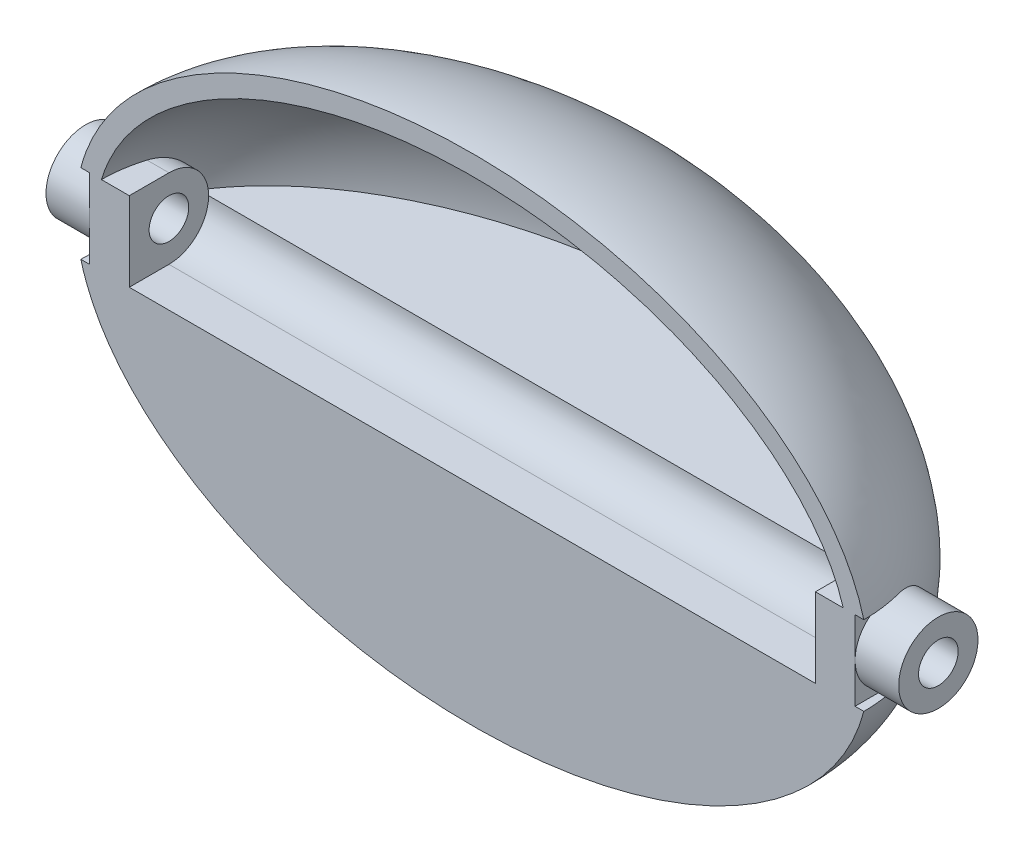
SolidWorks part; units mm, degrees
ref_plane "前视基准面" through (0, 0, 0) normal (0, 0, 1) x (1, 0, 0)
ref_plane "上视基准面" through (0, 0, 0) normal (0, 1, 0) x (1, 0, 0)
ref_plane "右视基准面" through (0, 0, 0) normal (1, 0, 0) x (0, 0, -1)
sketch "草图1" plane through (0, 0, 0) normal (0, 1, 0) x (1, 0, 0)
  line L0 (-376.7768, 0) -> (373.0191, 0) construction
  ellipse E0 centre (0, 0) end of major axis (200, 0) minor radius 125
  dimension "D1" = 250
  dimension "D2" = 400
revolve "旋转3" add sketch "草图1" angle 360 about L0
other "使用曲面切除1" flip cut yes
ref_plane "基准面1" through (0, -120, 0) normal (0, 1, 0) x (1, 0, 0)
sketch "草图2" plane through (0, -120, 0) normal (0, 1, 0) x (1, 0, 0)
  line L0 (-220.1966, 60) -> (220.5469, 60) construction
  line L1 (-137.5, 0) -> (137.5, 0) construction
  dimension "D1" = 60
ref_plane "基准面2" through (0, -125.2463, -45.5859) normal (0, 0.9397, 0.342) x (1, 0, 0)
sketch "草图3" plane through (0, -125.2463, -45.5859) normal (0, 0.9397, 0.342) x (1, 0, 0)
  line L0 (242.644, 40.5999) -> (-241.7114, 40.5999) construction
  line L1 (242.644, 63.6227) -> (-241.7114, 63.6227) construction
  line L2 (242.644, 23.6227) -> (-241.7114, 23.6227) construction
  line L3 (0, 214.3253) -> (0, -90.9867) construction
  line L4 (20, 214.3253) -> (20, -90.9867) construction
  line L5 (-20, 214.3253) -> (-20, -90.9867) construction
  line L6 (20, 63.6227) -> (-20, 63.6227)
  line L7 (-20, 63.6227) -> (-20, 23.6227)
  line L8 (-20, 23.6227) -> (20, 23.6227)
  line L9 (20, 23.6227) -> (20, 63.6227)
  dimension "D1" = 40
  dimension "D2" = 40
extrude "切除-拉伸1" cut sketch "草图3" along normal blind 70
sketch "草图4" plane through (0, 0, 0) normal (0, 0, 1) x (1, 0, 0)
  line L0 (-200, 0) -> (200, 0) construction
  line L1 (-189.2649, 10) -> (189.2649, 10)
  ellipse E1 centre (0, 0) end of major axis (200, 0) minor radius 125 (200, 0) -> (-200, 0) ccw construction
  ellipse E2 centre (0, 0) end of major axis (200, 0) minor radius 125 (200, 0) -> (-200, 0) ccw construction
  spline S0 degree 1 poles (189.2649, 10) (-189.2649, 10) knots 0 0 1 1 construction
  spline S1 degree 3 poles (189.2649, 10) (189.0166, 11.6856) (188.3998, 15.0246) (186.6607, 21.7177) (183.544, 30.0287) (178.2804, 39.8711) (169.2381, 52.6988) (154.19, 67.9384) (130.6173, 84.1337) (102.3316, 97.5039) (70.3463, 107.4698) (35.8196, 113.6157) (0, 115.6921) (-35.8196, 113.6157) (-70.3463, 107.4698) (-102.3316, 97.5039) (-130.6173, 84.1337) (-154.19, 67.9384) (-169.2381, 52.6988) (-178.2804, 39.8711) (-183.544, 30.0287) (-186.6607, 21.7177) (-188.3998, 15.0246) (-189.0166, 11.6856) (-189.2649, 10) knots 0.091785 0.091785 0.091785 0.091785 0.138004 0.184223 0.276661 0.369099 0.461538 0.646414 0.83129 1.016167 1.201043 1.38592 1.570796 1.755673 1.940549 2.125426 2.310302 2.495179 2.680055 2.772493 2.864932 2.95737 3.003589 3.049808 3.049808 3.049808 3.049808
  dimension "D1" = 10
revolve "切除-旋转1" cut sketch "草图4" angle 90 about L0 reverse direction yes
ref_plane "基准面3" through (215, 0, 0) normal (1, 0, 0) x (0, 0, -1)
sketch "草图5" plane through (215, 0, 0) normal (1, 0, 0) x (0, 0, -1)
  line L0 (-46.4571, 0) -> (160.9723, 0) construction
  line L1 (0, 20) -> (40, 20) construction
  line L2 (0, 137.5) -> (0, -137.5) construction
  line L3 (40, 20) -> (40, -20) construction
  line L4 (40, -20) -> (0, -20) construction
  line L5 (0, -20) -> (0, 20)
  line L6 (20, 20) -> (20, -20) construction
  line L7 (20, 20) -> (0, 20)
  line L8 (20, -20) -> (0, -20)
  line L9 (0, 20) -> (0, -20)
  arc A1 (20, 20) -> (20, -20) centre (20, 0) cw
  dimension "D1" = 40
  dimension "D2" = 40
extrude "切除-拉伸2" cut sketch "草图5" against normal through all contours A1 L7 L5 L8
sketch "草图6" plane through (215, 0, 0) normal (1, 0, 0) x (0, 0, -1)
  line L0 (20, -20) -> (0, -20) construction
  line L1 (20, 20) -> (0, 20) construction
  line L2 (0, -20) -> (0, 20) construction
  line L3 (20, -20) -> (0, -20)
  line L4 (20, 20) -> (0, 20)
  line L5 (0, -20) -> (0, 20)
  arc A0 (20, -20) -> (20, 20) centre (20, 0) ccw construction
  arc A1 (20, -20) -> (20, 20) centre (20, 0) ccw
extrude "凸台-拉伸1" add sketch "草图6" against normal blind 42
mirror "镜向1" about plane through (0, 0, 0) normal (1, 0, 0) of "凸台-拉伸1"
sketch "草图7" plane through (215, 0, 0) normal (1, 0, 0) x (0, 0, -1)
  circle A0 centre (20, 0) radius 10
  dimension "D1" = 20
extrude "切除-拉伸3" cut sketch "草图7" against normal blind 440
sketch "草图8" plane through (215, 0, 0) normal (1, 0, 0) x (0, 0, -1)
  line L0 (20, 20) -> (0, 20)
  line L1 (0, 137.5) -> (0, -137.5) construction
  line L2 (0, 20) -> (0, -20)
  line L3 (0, -20) -> (20, -20)
  arc A0 (20, 20) -> (20, -20) centre (20, 0) ccw
  line M3 (20, 20) -> (0, 20)
  line M4 (0, 20) -> (0, -20)
  line M5 (0, -20) -> (20, -20)
extrude "切除-拉伸4" cut sketch "草图8" against normal blind 22 contours A0 M3 M4 | A0 L2 M5
mirror "镜向2" about plane through (0, 0, 0) normal (1, 0, 0) of "切除-拉伸4"
ref_plane "基准面4" through (0, -126.6422, -22.3304) normal (0, 0.9848, 0.1736) x (1, 0, 0)
sketch "草图9" plane through (0, -126.6422, -22.3304) normal (0, 0.9848, 0.1736) x (1, 0, 0)
  line L0 (0, 135.7879) -> (0, -70.3108) construction
  line L1 (30, 28.0147) -> (-30, 28.0147)
  line L2 (-30, 28.0147) -> (-30, -1.9853)
  line L3 (-30, -1.9853) -> (30, -1.9853)
  line L4 (30, -1.9853) -> (30, 28.0147)
  dimension "D1" = 60
  dimension "D2" = 30
extrude "切除-拉伸5" cut sketch "草图9" along normal blind 30
